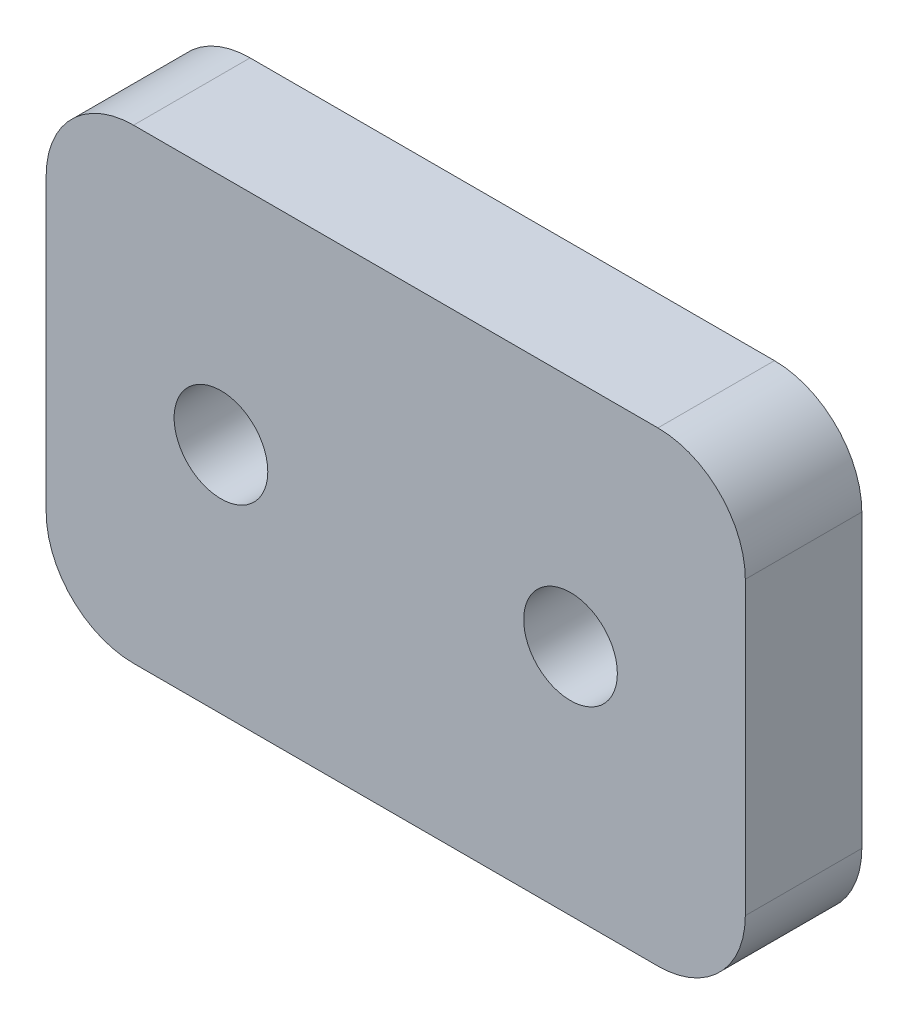
SolidWorks part; units mm, degrees
material "6061-T6 (SS)"
ref_plane "Front Plane" through (0, 0, 0) normal (0, 0, 1) x (1, 0, 0)
ref_plane "Top Plane" through (0, 0, 0) normal (0, 1, 0) x (1, 0, 0)
ref_plane "Right Plane" through (0, 0, 0) normal (1, 0, 0) x (0, 0, -1)
sketch "Sketch2" plane through (0, 0, 0) normal (0, 0, 1) x (1, 0, 0)
  line L1 (0, 0) -> (38.1, 0)
  line L2 (0, 0) -> (0, 25.4)
  line L3 (0, 25.4) -> (38.1, 25.4)
  line L4 (38.1, 0) -> (38.1, 25.4)
  circle A4 centre (9.525, 12.7) radius 2.5527
  circle A5 centre (28.575, 12.7) radius 2.5527
  point P9 (19.6775, 12.1717)
  point P10 (6.9775, 12.1717)
  point P11 (0, 0)
  point P12 (0, 12.7)
  point P13 (13.4009, 11.6766)
  point P14 (26.7458, 12.7)
  point P15 (25.6815, 12.7)
  point P16 (6.7858, 12.7)
  dimension "D3" = 19.05
  dimension "D4" = 5.1054
  dimension "D1" = 25.4
  dimension "D2" = 38.1
  dimension ".375" = 9.525
extrude "Boss-Extrude1" add sketch "Sketch2" along normal blind 6.35
fillet "Fillet1" radius 4.7625 4 edges at (0, 25.4, 3.175) (0, 0, 3.175) (38.1, 0, 3.175) (38.1, 25.4, 3.175)
